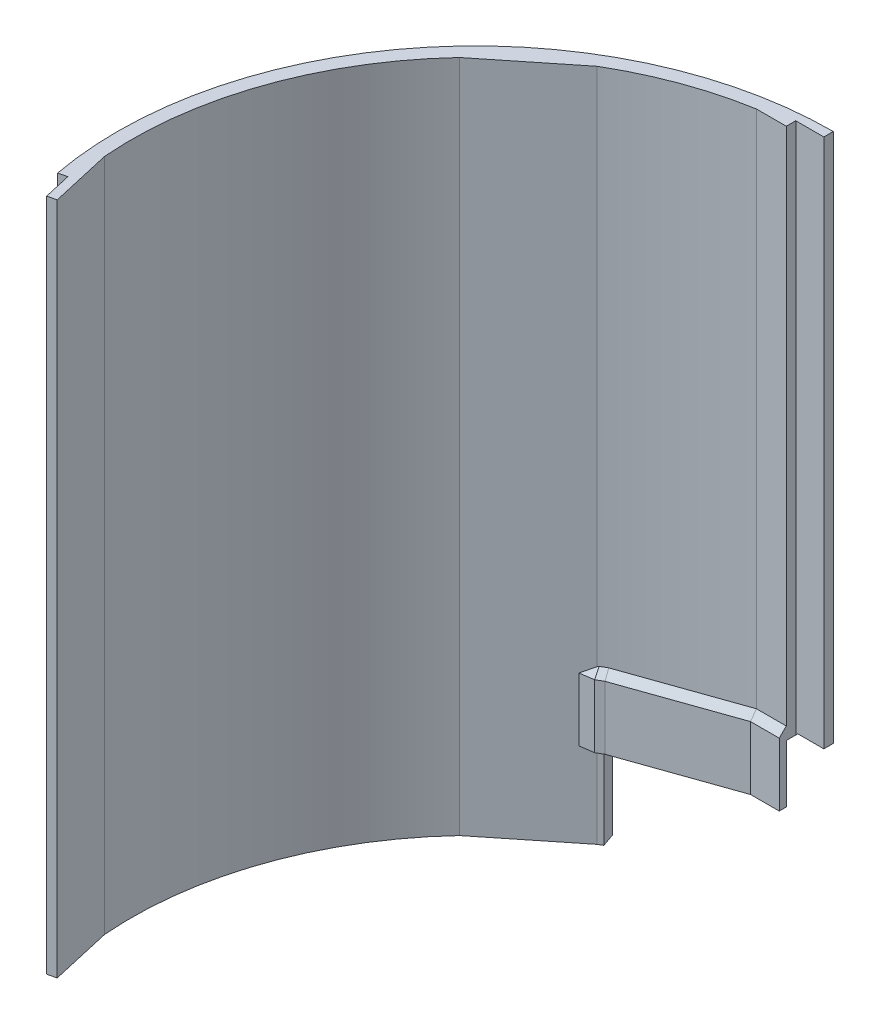
SolidWorks part; units mm, degrees
ref_plane "Спереди" through (0, 0, 0) normal (0, 0, 1) x (1, 0, 0)
ref_plane "Сверху" through (0, 0, 0) normal (0, 1, 0) x (1, 0, 0)
ref_plane "Справа" through (0, 0, 0) normal (1, 0, 0) x (0, 0, -1)
sketch "Эскиз1" plane through (0, 0, 0) normal (0, 1, 0) x (1, 0, 0)
  line L0 (0, -1000) -> (0, 49000) construction
  line L1 (48.839, -3.9694) -> (46.8431, -12.7269) construction
  line L2 (48.0618, -13.0047) -> (48.9507, -9.1047) construction
  line L3 (46.8431, -12.7269) -> (48.0618, -13.0047) construction
  line L4 (48.9507, -9.1047) -> (50.1312, -9.3737) construction
  line L5 (48.839, -3.9694) -> (46.8431, -12.7269) construction
  line L6 (48.0618, -13.0047) -> (48.9507, -9.1047) construction
  line L7 (46.8431, -12.7269) -> (48.0618, -13.0047) construction
  line L8 (48.9507, -9.1047) -> (50.1312, -9.3737) construction
  line L9 (-48.839, -3.9694) -> (-46.8431, -12.7269)
  line L10 (-46.8431, -12.7269) -> (-48.0618, -13.0047)
  line L11 (-48.0618, -13.0047) -> (-48.9507, -9.1047)
  line L12 (-48.9507, -9.1047) -> (-50.1312, -9.3737)
  line L13 (-4, 49.65) -> (-4, 48.3) construction
  line L14 (0, 49.65) -> (-4, 49.65) construction
  line L16 (-4, 49.65) -> (-4, 48.3)
  line L17 (0, 49.65) -> (-4, 49.65)
  line L19 (-35.7629, 33.4965) -> (-24.8621, 42.2241) construction
  line L20 (-35.7629, 33.4965) -> (-24.8621, 42.2241)
  line L21 (-8.2529, 48.3) -> (8.2529, 48.3) construction
  line L23 (-8.2529, 48.3) -> (-4, 48.3)
  line L25 (0, 48.3) -> (8.2529, 48.3) construction
  line L26 (-4, 48.3) -> (0, 48.3) construction
  line L27 (0, 51) -> (0, 49.65) construction
  line L28 (0, 51) -> (0, 49.65)
  circle A0 centre (0, 0) radius 51 construction
  arc A1 (0, 51) -> (-50.1312, -9.3737) centre (0, 0) ccw
  arc A2 (48.839, -3.9694) -> (35.7629, 33.4965) centre (0, 0) ccw construction
  arc A3 (48.839, -3.9694) -> (35.7629, 33.4965) centre (0, 0) ccw construction
  arc A4 (-48.839, -3.9694) -> (-35.7629, 33.4965) centre (0, 0) cw
  arc A5 (0, -51) -> (50.1312, -9.3737) centre (0, 0) ccw construction
  arc A6 (50.1312, -9.3737) -> (0, 51) centre (0, 0) ccw construction
  arc A7 (-23.8222, 42.8194) -> (-24.8621, 42.2241) centre (0, 0) ccw construction
  arc A8 (-23.8222, 42.8194) -> (-24.8621, 42.2241) centre (0, 0) ccw
  arc A9 (-50.1312, -9.3737) -> (0, -51) centre (0, 0) ccw construction
  arc A10 (-23.8222, 42.8194) -> (-8.2529, 48.3) centre (0, 0) cw
extrude "Бобышка-Вытянуть1" add sketch "Эскиз1" along normal up to surface (96 mm away)
ref_plane "Плоскость4" through (-12.7171, 0, -36.1271) normal (0.332, 0, 0.9433) x (0.9433, 0, -0.332)
sketch "Эскиз2" plane through (-12.7171, 0, -36.1271) normal (0.332, 0, 0.9433) x (0.9433, 0, -0.332)
  line L0 (8.7529, 0) -> (8.7529, 17.5)
  line L1 (8.7529, 17.5) -> (-5.46, 17.5)
  line L2 (-5.46, 17.5) -> (-8.7529, 14.2071)
  line L3 (-8.7529, 14.2071) -> (-8.7529, 0)
  line L4 (-8.7529, 0) -> (-8.2529, 0)
  line L5 (8.2529, 17) -> (-5.2529, 17)
  line L6 (-5.2529, 17) -> (-8.2529, 14)
  line L7 (-8.2529, 14) -> (-8.2529, 0)
  line L8 (-8.2529, 0) -> (8.2529, 0)
  line L9 (8.2529, 0) -> (8.2529, 17)
  line L10 (8.2529, 17) -> (-5.2529, 17) construction
  line L11 (-5.2529, 17) -> (-8.2529, 14) construction
  line L12 (-8.2529, 14) -> (-8.2529, 0) construction
  line L13 (-8.2529, 0) -> (8.2529, 0)
  line L14 (8.2529, 0) -> (8.2529, 17) construction
  line L15 (8.2529, 0) -> (8.7529, 0)
  dimension "D1" = 0
  dimension "D2" = 0.5
extrude "Вырез-Вытянуть1" cut sketch "Эскиз2" against normal through all
sketch "Эскиз3" plane through (0, 0, -48.3) normal (0, 0, 1) x (1, 0, 0)
  line L2 (0, 20) -> (0, 0)
  line L3 (3.5, 20) -> (0, 20) construction
  line L4 (0, 0) -> (8.2529, 0) construction
  line L5 (0, 95.8803) -> (0, 20) construction
  line L6 (0, 20.5) -> (-3.7071, 20.5)
  line L7 (-3.7071, 20.5) -> (-6.7071, 17.5)
  line L8 (-8.2529, 0) -> (8.2529, 0)
  line L9 (8.2529, 0) -> (8.2529, 17)
  line L10 (8.2529, 17) -> (6.5, 17)
  line L11 (6.5, 17) -> (3.5, 20)
  line L12 (3.5, 20) -> (-3.5, 20)
  line L13 (-3.5, 20) -> (-6.5, 17)
  line L14 (-6.5, 17) -> (-8.2529, 17)
  line L15 (-8.2529, 17) -> (-8.2529, 0)
  line L16 (-8.2529, 0) -> (0, 0)
  line L17 (8.2529, 0) -> (8.2529, 17) construction
  line L18 (8.2529, 17) -> (6.5, 17) construction
  line L19 (6.5, 17) -> (3.5, 20) construction
  line L20 (0, 20) -> (-3.5, 20) construction
  line L21 (-3.5, 20) -> (-6.5, 17) construction
  line L22 (-6.5, 17) -> (-8.2529, 17) construction
  line L23 (-8.2529, 17) -> (-8.2529, 0) construction
  line L24 (-6.7071, 17.5) -> (-8.7529, 17.5)
  line L25 (-8.7529, 17.5) -> (-8.7529, 0)
  line L26 (-8.7529, 0) -> (-8.2529, 0)
  line L27 (0, 20.5) -> (0, 20)
  line M10 (-8.2529, 0) -> (8.2529, 0)
  line M14 (3.5, 20) -> (-3.5, 20)
  line M15 (-3.5, 20) -> (-6.5, 17)
  line M16 (-6.5, 17) -> (-8.2529, 17)
  line M17 (-8.2529, 17) -> (-8.2529, 0)
  dimension "D1" = 0
  dimension "D2" = 0.5
extrude "Вырез-Вытянуть2" cut sketch "Эскиз3" against normal through all contours L27 L6 L7 L24 L25 L26 M17 M16 M15 M14 | L2 M14 M15 M16 M17 M10
sketch "Эскиз4" plane through (0, 12, 0) normal (0, 1, 0) x (1, 0, 0)
  line L0 (0, -1000) -> (0, 49000) construction
  line L1 (-4, 47.3) -> (0, 47.3) construction
  line L2 (0, 48.3) -> (-4, 48.3) construction
  line L3 (-8.082, 47.3) -> (-20.6603, 42.8723)
  line L4 (-20.6603, 42.8723) -> (-23.4097, 41.9045)
  line L5 (-24.3547, 41.3624) -> (-26.3116, 41.0636)
  line L6 (-26.3116, 41.0636) -> (-24.8621, 42.2241)
  line L7 (-23.8222, 42.8194) -> (-20.9924, 43.8155)
  line L8 (-20.9924, 43.8155) -> (-8.2529, 48.3)
  line L9 (8.2529, 48.3) -> (-4, 48.3)
  line L10 (20.9924, 43.8155) -> (8.2529, 48.3)
  line L11 (23.8222, 42.8194) -> (20.9924, 43.8155)
  line L12 (26.3116, 41.0636) -> (24.8621, 42.2241)
  line L13 (24.3547, 41.3624) -> (26.3116, 41.0636)
  line L14 (20.6603, 42.8723) -> (23.4097, 41.9045)
  line L15 (8.082, 47.3) -> (20.6603, 42.8723)
  line L16 (-4, 47.3) -> (8.082, 47.3)
  line L17 (-4, 48.3) -> (-4, 47.3)
  line L18 (8.2529, 48.3) -> (0, 48.3) construction
  line L19 (20.9924, 43.8155) -> (8.2529, 48.3) construction
  line L20 (23.8222, 42.8194) -> (20.9924, 43.8155) construction
  line L21 (26.3116, 41.0636) -> (24.8621, 42.2241) construction
  line L22 (24.3547, 41.3624) -> (26.3116, 41.0636) construction
  line L23 (20.6603, 42.8723) -> (23.4097, 41.9045) construction
  line L24 (8.082, 47.3) -> (20.6603, 42.8723) construction
  line L25 (-8.082, 47.3) -> (-4, 47.3)
  line L26 (-4, 48.3) -> (-4, 47.3)
  line L27 (-4, 47.3) -> (0, 47.3) construction
  line L28 (0, 47.3) -> (8.082, 47.3) construction
  line L29 (0, 48.3) -> (-4, 48.3) construction
  line L30 (-4, 48.3) -> (-8.2529, 48.3)
  arc A0 (-24.3547, 41.3624) -> (-23.4097, 41.9045) centre (0, 0) cw
  arc A1 (-24.8621, 42.2241) -> (-23.8222, 42.8194) centre (0, 0) cw
  arc A2 (24.8621, 42.2241) -> (23.8222, 42.8194) centre (0, 0) ccw
  arc A3 (24.3547, 41.3624) -> (23.4097, 41.9045) centre (0, 0) ccw
  arc A4 (24.8621, 42.2241) -> (23.8222, 42.8194) centre (0, 0) ccw construction
  arc A5 (24.3547, 41.3624) -> (23.4097, 41.9045) centre (0, 0) ccw
  line M32 (8.2529, 48.3) -> (-8.2529, 48.3)
  line M33 (-8.2529, 48.3) -> (-23.8222, 42.8194)
  arc M34 (-23.8222, 42.8194) -> (-24.8621, 42.2241) centre (0, 0) ccw
  line M35 (-24.8621, 42.2241) -> (-35.7629, 33.4965)
  dimension "D1" = 0
extrude "Бобышка-Вытянуть2" add sketch "Эскиз4" along normal up to vertex (10 mm away) contours L5 A0 L4 L3 L25 L26 M32 M33 M34 M35
chamfer "Фаска1" distance 1 angle 45 4 edges at (-25.3331, 22, -41.213) (-23.8837, 22, -41.6361) (-15.7459, 22, -44.6022) (-6.041, 22, -47.3)
